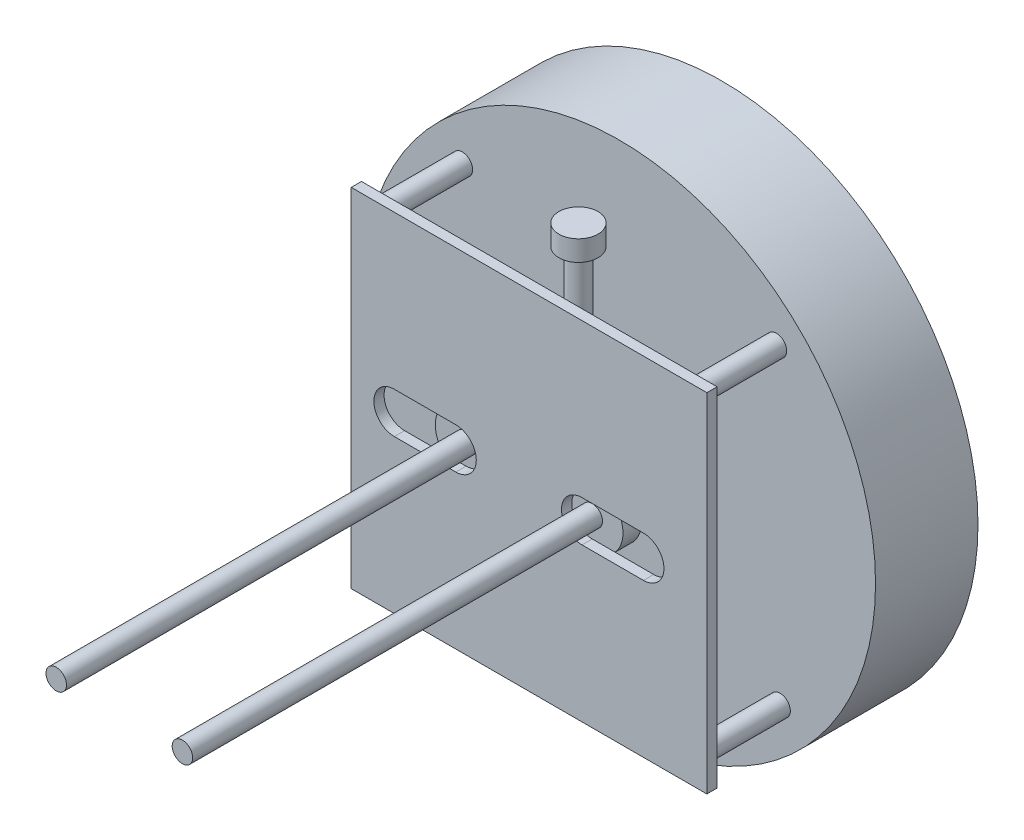
SolidWorks part; units mm, degrees
ref_plane "Front Plane" through (0, 0, 0) normal (0, 0, 1) x (1, 0, 0)
ref_plane "Top Plane" through (0, 0, 0) normal (0, 1, 0) x (1, 0, 0)
ref_plane "Right Plane" through (0, 0, 0) normal (1, 0, 0) x (0, 0, -1)
sketch "Sketch1" plane through (0, 0, 0) normal (0, 0, 1) x (1, 0, 0)
  circle A0 centre (0, 0) radius 125
  dimension "D1" = 250
extrude "Boss-Extrude1" add sketch "Sketch1" along normal blind 50
sketch "Sketch2" plane through (0, 0, 50) normal (0, 0, 1) x (1, 0, 0)
  line L0 (0, 0) -> (0, 84.2793) construction
  line L1 (0, 125) -> (125, 0) construction
  line L2 (125, 0) -> (0, -125) construction
  line L3 (0, -125) -> (-125, 0) construction
  line L4 (-125, 0) -> (0, 125) construction
  line L5 (-62.5, 62.5) -> (-76.6421, 76.6421) construction
  line L6 (62.5, 62.5) -> (76.6421, 76.6421) construction
  line L7 (62.5, -62.5) -> (78.4137, -74.6142) construction
  line L8 (-62.5, -62.5) -> (-76.6421, -76.6421) construction
  circle A0 centre (0, 0) radius 125 construction
  circle A1 centre (-76.6421, 76.6421) radius 5
  circle A2 centre (76.6421, 76.6421) radius 5
  circle A3 centre (78.4137, -74.6142) radius 5
  circle A4 centre (-76.6421, -76.6421) radius 5
  point P8 (-62.5, 62.5)
  point P11 (62.5, 62.5)
  point P12 (62.5, -62.5)
  point P13 (-62.5, -62.5)
  dimension "D5" = 10
  dimension "D6" = 10
  dimension "D7" = 10
  dimension "D8" = 10
  dimension "D1" = 20
  dimension "D2" = 20
  dimension "D3" = 20
  dimension "D4" = 20
extrude "Boss-Extrude2" add sketch "Sketch2" along normal blind 40
sketch "Sketch3" plane through (0, 0, 90) normal (0, 0, 1) x (1, 0, 0)
  line L1 (-85.8829, 84.5606) -> (87.6647, 84.5606)
  line L2 (-85.8829, 84.5606) -> (-85.8829, -85.0671)
  line L3 (-85.8829, -85.0671) -> (87.6647, -85.0671)
  line L4 (87.6647, 84.5606) -> (87.6647, -85.0671)
  point P4 (87.6647, -85.0671)
extrude "Boss-Extrude3" add sketch "Sketch3" along normal blind 5
sketch "Sketch4" plane through (0, 0, 95) normal (0, 0, 1) x (1, 0, 0)
  line L0 (-85.8829, -0.2532) -> (87.6647, -0.2532) construction
  line L1 (-85.8829, 84.5606) -> (-85.8829, -85.0671) construction
  line L2 (87.6647, -85.0671) -> (87.6647, 84.5606) construction
  line L3 (87.6647, -0.2532) -> (0.8909, 84.5606) construction
  line L4 (87.6647, 84.5606) -> (-85.8829, 84.5606) construction
  line L5 (0.8909, 84.5606) -> (0.8909, -85.0671) construction
  line L6 (-85.8829, -85.0671) -> (87.6647, -85.0671) construction
  line L7 (-64.8577, -0.2532) -> (-34.8577, -0.2532) construction
  line L8 (-64.8577, 9.7468) -> (-34.8577, 9.7468)
  line L9 (-64.8577, -10.2532) -> (-34.8577, -10.2532)
  line L10 (26.7271, -0.2532) -> (56.7271, -0.2532) construction
  line L11 (26.7271, 9.7468) -> (56.7271, 9.7468)
  line L12 (26.7271, -10.2532) -> (56.7271, -10.2532)
  arc A0 (-64.8577, 9.7468) -> (-64.8577, -10.2532) centre (-64.8577, -0.2532) ccw
  arc A1 (-34.8577, -10.2532) -> (-34.8577, 9.7468) centre (-34.8577, -0.2532) ccw
  arc A2 (26.7271, 9.7468) -> (26.7271, -10.2532) centre (26.7271, -0.2532) ccw
  arc A3 (56.7271, -10.2532) -> (56.7271, 9.7468) centre (56.7271, -0.2532) ccw
  point P14 (-49.8577, -0.2532)
  point P21 (41.7271, -0.2532)
  dimension "D3" = 10
  dimension "D4" = 10
  dimension "D1" = 30
  dimension "D2" = 30
extrude "Cut-Extrude1" cut sketch "Sketch4" against normal blind 19
sketch "Sketch5" plane through (0, 0, 90) normal (0, 0, -1) x (-1, 0, 0)
  circle A0 centre (-26.7271, -0.2532) radius 15
  circle A1 centre (34.8577, -0.2532) radius 15
  dimension "D1" = 30
  dimension "D2" = 30
extrude "Boss-Extrude4" add sketch "Sketch5" along normal blind 9
sketch "Sketch6" plane through (0, 0, 90) normal (0, 0, 1) x (1, 0, 0)
  circle A0 centre (26.7271, -0.2532) radius 5
  circle A1 centre (-34.8577, -0.2532) radius 5
  dimension "D1" = 10
  dimension "D2" = 10
extrude "Boss-Extrude5" add sketch "Sketch6" along normal blind 200
sketch "Sketch7" plane through (0, 0, 50) normal (0, 0, 1) x (1, 0, 0)
  line L0 (0, -85.3484) -> (0, 84.992) construction
  circle A0 centre (0, 30) radius 5
  circle A1 centre (0, -30) radius 5
  dimension "D3" = 10
  dimension "D4" = 10
  dimension "D1" = 30
  dimension "D2" = 30
extrude "Boss-Extrude6" add sketch "Sketch7" along normal blind 20
sketch "Sketch8" plane through (0, 0, 70) normal (0, 0, 1) x (1, 0, 0)
  line L0 (0, 30) -> (0, 100)
  line L1 (0, -30) -> (0, -100)
  line L2 (0, 30) -> (0, 25)
  circle A0 centre (0, 30) radius 5 construction
  point P7 (0, 25)
  dimension "D1" = 70
  dimension "D2" = 70
sweep "Sweep1" add path "Sketch8" circular profile diameter 10 parameters "D3"=10
sweep "Sweep2" add path "Sketch8<3>" circular profile diameter 10 parameters "D3"=10
sketch "Sketch8<3>" plane through (0, 0, 70) normal (0, 0, 1) x (1, 0, 0) same geometry as "Sketch8"
sweep "Sweep3" add path "Sketch8<4>" circular profile diameter 10 parameters "D3"=10
sketch "Sketch8<4>" plane through (0, 0, 70) normal (0, 0, 1) x (1, 0, 0) same geometry as "Sketch8"
sketch "Sketch46" plane through (0, 100, 0) normal (0, 1, 0) x (1, 0, 0)
  circle A0 centre (0, -70) radius 9.5454
extrude "Boss-Extrude7" add sketch "Sketch46" along normal blind 0.006 and the other way blind 10
sketch "Sketch47" plane through (0, -100, 0) normal (0, -1, 0) x (1, 0, 0)
  circle A0 centre (0, 70) radius 9.4872
extrude "Boss-Extrude8" add sketch "Sketch47" along normal blind 0.006 and the other way blind 10
